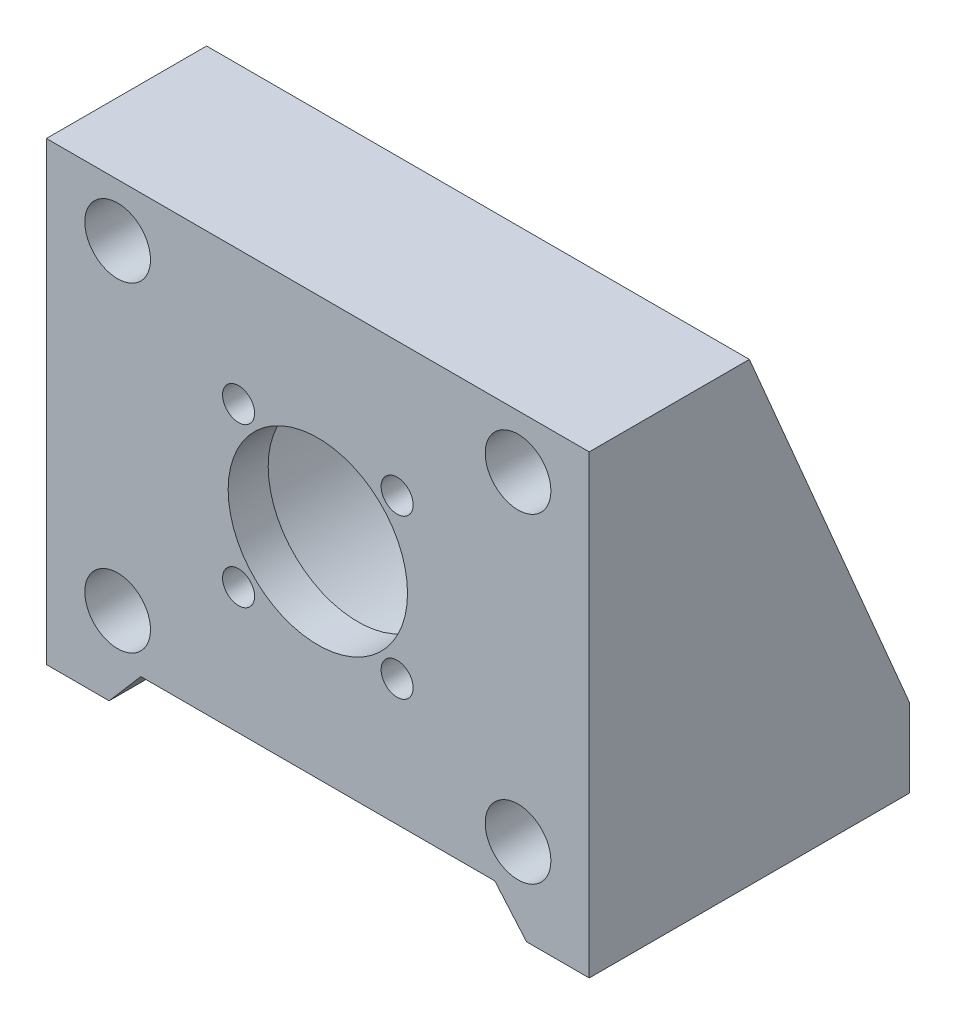
SolidWorks part; units mm, degrees
ref_plane "Front Plane" through (0, 0, 0) normal (0, 0, 1) x (1, 0, 0)
ref_plane "Top Plane" through (0, 0, 0) normal (0, 1, 0) x (1, 0, 0)
ref_plane "Right Plane" through (0, 0, 0) normal (1, 0, 0) x (0, 0, -1)
sketch "PosicionAgujeros" plane through (0, 0, 0) normal (0, 0, 1) x (1, 0, 0)
  line L1 (25, -20) -> (-25, -20) construction
  line L2 (25, -20) -> (25, 20) construction
  line L3 (25, 20) -> (-25, 20) construction
  line L4 (-25, -20) -> (-25, 20) construction
  line L5 (25, -20) -> (-25, 20) construction
  line L6 (25, 20) -> (-25, -20) construction
  line L9 (0, 0) -> (9.8995, 9.8995) construction
  circle A1 centre (25, 20) radius 4 construction
  circle A3 centre (0, 0) radius 11 construction
  circle A4 centre (0, 0) radius 14 construction
  circle A6 centre (0, 0) radius 18 construction
  circle A7 centre (9.8995, 9.8995) radius 2 construction
  point P2 (0, 0)
  point P8 (25, 20)
  point P11 (-25, -20)
  point P12 (25, -20)
  point P13 (9.8995, 9.8995)
  point P18 (-25, 20)
  dimension "D4" = 8
  dimension "D5" = 45
  dimension "D6" = 22
  dimension "D7" = 28
  dimension "D10" = 36
  dimension "D11" = 4
  dimension "D2" = 50
  dimension "D3" = 40
sketch "Croquis2" plane through (0, 0, 0) normal (0, 0, 1) x (1, 0, 0)
  line L0 (25, 20) -> (-25, -20) construction
  line L1 (0, -11.2) -> (0, -25.6668)
  line L2 (0, -25.6668) -> (22.0995, -25.6668)
  line L3 (22.0995, -25.6668) -> (26.0623, -30.2693)
  line L4 (26.0623, -30.2693) -> (33.8909, -30.2693)
  line L5 (33.8909, -30.2693) -> (33.8909, 26.6303)
  line L6 (33.8909, 26.6303) -> (0, 26.6303)
  line L7 (0, 26.6303) -> (0, 11.2)
  arc A0 (0, 11.2) -> (0, -11.2) centre (0, 0) cw
  dimension "D1" = 11.2
extrude "Saliente-Extruir1" add sketch "Croquis2" against normal blind 35 and the other way blind 5
mirror "Simetría1" about plane through (0, 0, 0) normal (1, 0, 0) of "Saliente-Extruir1"
sketch "Croquis5" plane through (0, 0, 0) normal (0, 0, 1) x (1, 0, 0)
  circle A0 centre (0, 0) radius 18.1
  dimension "D1" = 36.2
extrude "Cortar-Extruir1" cut sketch "Croquis5" against normal blind 35
chamfer "Chaflán1" distance 20 angle 67 1 edges at (0, 26.6303, -35) first distance on face at (0, 26.6303, -15)
hole_wizard "Taladro1" positions "Croquis3" profile "Croquis4" legacy
sketch "Croquis3" plane through (0, 0, 5) normal (0, 0, 1) x (1, 0, 0)
  point P0 (25, -20)
  point P3 (25, 20)
  point P6 (-25, 20)
  point P9 (-25, -20)
sketch "Croquis4" plane through (25, -20, 5) normal (1, 0, 0) x (0, -1, 0)
  line L0 (0, 0) -> (0, 15)
  line L1 (0, 15) -> (4.1, 15)
  line L2 (4.1, 15) -> (4.1, 0)
  line L3 (4.1, 0) -> (0, 0)
  line L4 (0, 110) -> (0, -10) construction
  dimension "Diámetro" = 8.2
  dimension "Profundidad" = 15
hole_wizard "Taladro3" positions "Croquis10" profile "Croquis11" legacy end condition through all
sketch "Croquis10" plane through (0, 0, 5) normal (0, 0, 1) x (1, 0, 0)
  point P0 (9.8995, 9.8995)
sketch "Croquis11" plane through (9.8995, 9.8995, 5) normal (1, 0, 0) x (0, -1, 0)
  line L0 (0, 0) -> (0, 40)
  line L1 (0, 40) -> (2, 40)
  line L2 (2, 40) -> (2, 0)
  line L3 (2, 0) -> (0, 0)
  line L4 (0, 110) -> (0, -10) construction
  dimension "Diámetro" = 4
  dimension "Profundidad" = 40
pattern_circular "MatrizC2" count 4 over 360 about axis through (0, 0, -35) along (0, 0, 1) of "Taladro3"
